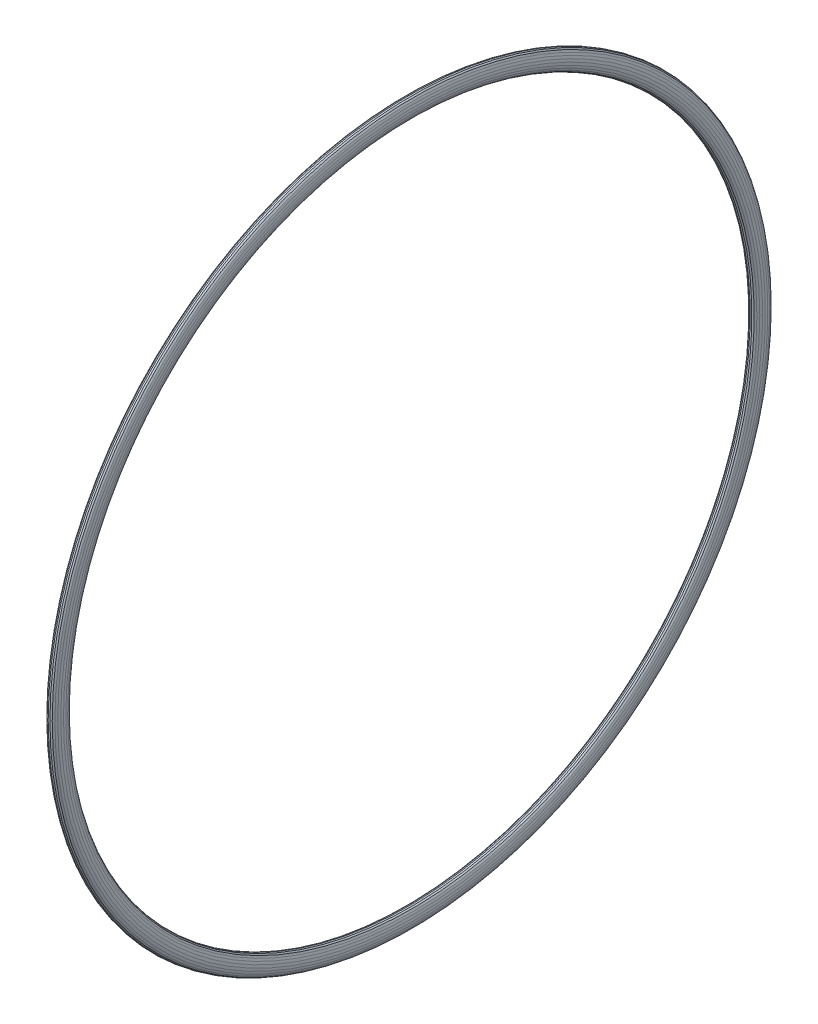
SolidWorks part; units mm, degrees
ref_plane "Front Plane" through (0, 0, 0) normal (0, 0, 1) x (1, 0, 0)
ref_plane "Top Plane" through (0, 0, 0) normal (0, 1, 0) x (1, 0, 0)
ref_plane "Right Plane" through (0, 0, 0) normal (1, 0, 0) x (0, 0, -1)
sketch "O_Ring_Inner Sketch" plane through (0, 0, 0) normal (0, 0, 1) x (1, 0, 0)
  line L0 (-1000, 0) -> (1000, 0) construction
  line L1 (-1.955, 62.78) -> (-1.9218, 63.2355)
  line L2 (-1.9218, 63.2355) -> (-1.8244, 63.6601)
  line L3 (-1.8244, 63.6601) -> (-1.6694, 64.0246)
  line L4 (-1.6694, 64.0246) -> (-1.4675, 64.3043)
  line L5 (-1.4675, 64.3043) -> (-1.2323, 64.4801)
  line L6 (-1.2323, 64.4801) -> (-0.98, 64.5401)
  line L7 (-0.98, 64.5401) -> (-0.7277, 64.4801)
  line L8 (-0.7277, 64.4801) -> (-0.4925, 64.3043)
  line L9 (-0.4925, 64.3043) -> (-0.2906, 64.0246)
  line L10 (-0.2906, 64.0246) -> (-0.1356, 63.6601)
  line L11 (-0.1356, 63.6601) -> (-0.0382, 63.2355)
  line L12 (-0.0382, 63.2355) -> (-0.005, 62.78)
  line L13 (-0.005, 62.78) -> (-0.0382, 62.3245)
  line L14 (-0.0382, 62.3245) -> (-0.1356, 61.8999)
  line L15 (-0.1356, 61.8999) -> (-0.2906, 61.5354)
  line L16 (-0.2906, 61.5354) -> (-0.4925, 61.2557)
  line L17 (-0.4925, 61.2557) -> (-0.7277, 61.0799)
  line L18 (-0.7277, 61.0799) -> (-0.98, 61.0199)
  line L19 (-0.98, 61.0199) -> (-1.2323, 61.0799)
  line L20 (-1.2323, 61.0799) -> (-1.4675, 61.2557)
  line L21 (-1.4675, 61.2557) -> (-1.6694, 61.5354)
  line L22 (-1.6694, 61.5354) -> (-1.8244, 61.8999)
  line L23 (-1.8244, 61.8999) -> (-1.9218, 62.3245)
  line L24 (-1.9218, 62.3245) -> (-1.955, 62.78)
revolve "O_Ring_Inner" add sketch "O_Ring_Inner Sketch" angle 360 about L0
ref_axis "Engine Axis" through (0.0925, 0, 0) along (-1, 0, 0)
